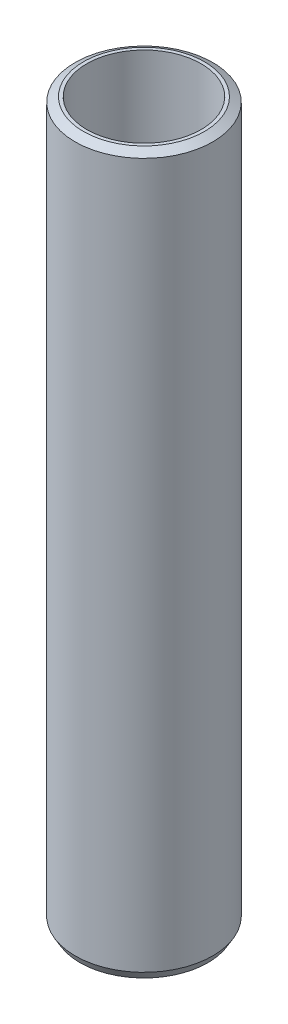
SolidWorks part; units mm, degrees
ref_plane "Front Plane" through (0, 0, 0) normal (0, 0, 1) x (1, 0, 0)
ref_plane "Top Plane" through (0, 0, 0) normal (0, 1, 0) x (1, 0, 0)
ref_plane "Right Plane" through (0, 0, 0) normal (1, 0, 0) x (0, 0, -1)
sketch "Sketch1" plane through (0, 0, 0) normal (0, 1, 0) x (1, 0, 0)
  circle A0 centre (0, 0) radius 57.5
  dimension "SHAFT_OD" = 115
extrude "Boss-Extrude1" add sketch "Sketch1" along normal blind 600
sketch "Sketch2" plane through (0, 0, 0) normal (0, 1, 0) x (1, 0, 0)
  circle A0 centre (0, 0) radius 47.749
  dimension "BORE_D" = 95.498
extrude "Cut-Extrude1" cut sketch "Sketch2" along normal through all
chamfer "Chamfer1" distance 4.0238 angle 60 2 edges at (0, 600, 57.5) (0, 0, 57.5) first distance on face at (0, 600, 57.5) first distance on face at (0, 0, 47.749)
